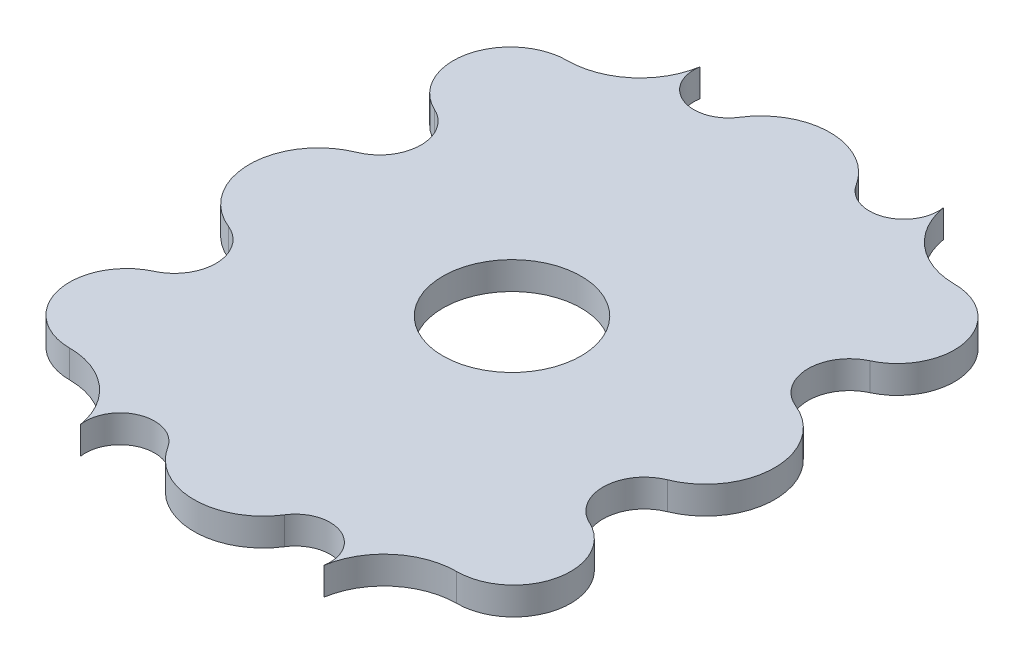
SolidWorks part; units mm, degrees
ref_plane "Alzado" through (0, 0, 0) normal (0, 0, 1) x (1, 0, 0)
ref_plane "Planta" through (0, 0, 0) normal (0, 1, 0) x (1, 0, 0)
ref_plane "Vista lateral" through (0, 0, 0) normal (1, 0, 0) x (0, 0, -1)
sketch "Croquis1" plane through (0, 0, 0) normal (0, 1, 0) x (1, 0, 0)
  line L0 (0, 138.5041) -> (0, -177.2184) construction
  line L2 (-70, -90) -> (-70, 90)
  line L4 (70, -90) -> (70, 90)
  line L5 (-70, -90) -> (70, 90) construction
  line L6 (-70, 90) -> (70, -90) construction
  line L7 (-103.4324, 0) -> (144.2109, 0) construction
  arc A1 (-21.1476, -103.3333) -> (21.1476, -103.3333) centre (0, -90) ccw
  arc A5 (-21.1476, -103.3333) -> (-44.0559, -112.0276) centre (-31.7214, -110) ccw
  arc A6 (-44.0559, -112.0276) -> (-70, -90) centre (-70, -116.2923) ccw
  arc A7 (21.1476, -103.3333) -> (44.0559, -112.0276) centre (31.7214, -110) cw
  arc A8 (44.0559, -112.0276) -> (70, -90) centre (70, -116.2923) cw
  arc A9 (44.0559, 112.0276) -> (70, 90) centre (70, 116.2923) ccw
  arc A10 (21.1476, 103.3333) -> (44.0559, 112.0276) centre (31.7214, 110) ccw
  arc A11 (-21.1476, 103.3333) -> (21.1476, 103.3333) centre (0, 90) cw
  arc A12 (-21.1476, 103.3333) -> (-44.0559, 112.0276) centre (-31.7214, 110) cw
  arc A13 (-44.0559, 112.0276) -> (-70, 90) centre (-70, 116.2923) cw
  point P0 (0, 0)
  point P14 (-25, -90)
  point P16 (-70, -90)
  dimension "D4" = 50
  dimension "D6" = 25
  dimension "D1" = 140
  dimension "D2" = 180
extrude "Saliente-Extruir1" add sketch "Croquis1" along normal blind 10
sketch "Croquis2" plane through (0, 10, 0) normal (0, 1, 0) x (1, 0, 0)
  line L0 (70, -90) -> (70, 90) construction
  line L1 (70, 90) -> (70, -90)
  line L2 (0, 152.4123) -> (0, -148.5895) construction
  line L3 (-96.3545, 0) -> (168.0513, 0) construction
  line L4 (-70, 90) -> (-70, -90)
  arc A0 (79.375, -23.1756) -> (79.375, 23.1756) centre (70, 0) ccw
  arc A1 (78.6826, 50.6858) -> (79.375, 23.1756) centre (85, 37.081) ccw
  arc A2 (78.6826, 50.6858) -> (70, 90) centre (70, 69.3841) ccw
  arc A3 (78.6826, -50.6858) -> (79.375, -23.1756) centre (85, -37.081) cw
  arc A4 (78.6826, -50.6858) -> (70, -90) centre (70, -69.3841) cw
  arc A5 (-78.6826, -50.6858) -> (-70, -90) centre (-70, -69.3841) ccw
  arc A6 (-78.6826, -50.6858) -> (-79.375, -23.1756) centre (-85, -37.081) ccw
  arc A7 (-79.375, -23.1756) -> (-79.375, 23.1756) centre (-70, 0) cw
  arc A8 (-78.6826, 50.6858) -> (-79.375, 23.1756) centre (-85, 37.081) cw
  arc A9 (-78.6826, 50.6858) -> (-70, 90) centre (-70, 69.3841) cw
  line M11 (-70, 90) -> (-70, -90)
  line M17 (70, -90) -> (70, 90)
  dimension "D1" = 50
  dimension "D2" = 30
extrude "Saliente-Extruir2" add sketch "Croquis2" against normal blind 10 contours A9 A8 M11 | A1 A2 L1 | L1 A3 A0 A1 | L4 A8 A7 A6 | A6 A5 L4 | A4 A3 M17 region at (78.5318, 10, -68.6447) region at (78.5318, 10, 68.6447) region at (80.2052, 10, 0) region at (-78.5318, 10, 68.6447) region at (-80.2052, 10, 0) region at (-78.5318, 10, -68.6447)
sketch "Croquis3" plane through (0, 10, 0) normal (0, 1, 0) x (1, 0, 0)
  circle A0 centre (0, 0) radius 25
  dimension "D1" = 50
extrude "Cortar-Extruir1" cut sketch "Croquis3" against normal blind 10
